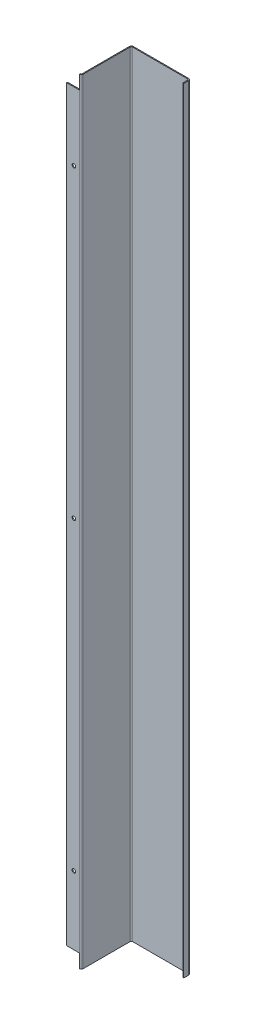
SolidWorks part; units mm, degrees
note: The reader was unsure of these and kept them because the rebuilt part matched: flange length of "Edge-Flange1", "Edge-Flange2", "Edge-Flange3".
material "Galvanized Steel"
ref_plane "Front Plane" through (0, 0, 0) normal (0, 0, 1) x (1, 0, 0)
ref_plane "Top Plane" through (0, 0, 0) normal (0, 1, 0) x (1, 0, 0)
ref_plane "Right Plane" through (0, 0, 0) normal (1, 0, 0) x (0, 0, -1)
sketch "Sketch1" plane through (0, 0, 0) normal (0, 0, 1) x (1, 0, 0)
  line L1 (101.6092, 293.6207) -> (-28.3908, 293.6207)
  line L2 (101.6092, 293.6207) -> (101.6092, -1406.3793)
  line L3 (101.6092, -1406.3793) -> (-28.3908, -1406.3793)
  line L4 (-28.3908, 293.6207) -> (-28.3908, -1406.3793)
  dimension "D1" = 130
  dimension "D2" = 1700
base flange "Base-Flange1" sketch "Sketch1" thickness 2 reverse thickness direction no parameters "D1"=0.5
edge flange "Edge-Flange1" sketch "Sketch8" flange angle 90 flange length 15 flange position material inside bend radius 2.5 thickness 2 relief obround parameters "D6"=10
sketch "Sketch8" plane through (101.6092, 0, 0) normal (1, 0, 0) x (0, 1, 0)
  line L2 (-1406.3793, 0) -> (-1406.3793, 13)
  line L3 (-1406.3793, 13) -> (293.6207, 13)
  line L4 (293.6207, 13) -> (293.6207, 0)
  line L7 (-1406.3793, 0) -> (293.6207, 0) construction
  line L8 (-1406.3793, 0) -> (293.6207, 0)
bend "EdgeBend1" bend radius 2.5 bend angle 90 parameters "D5"=1
edge flange "Edge-Flange2" sketch "Sketch11" flange angle 90 flange length 110 flange position material inside bend radius 2.5 thickness 2 relief obround parameters "D6"=10
sketch "Sketch11" plane through (-28.3908, 0, 0) normal (-1, 0, 0) x (0, -1, 0)
  line L2 (-293.6207, 0) -> (-293.6207, 108)
  line L3 (-293.6207, 108) -> (1406.3793, 108)
  line L4 (1406.3793, 108) -> (1406.3793, 0)
  line L5 (-293.6207, 0) -> (1406.3793, 0) construction
  line L6 (-293.6207, 0) -> (1406.3793, 0)
bend "EdgeBend2" bend radius 2.5 bend angle 90 parameters "D5"=2
edge flange "Edge-Flange3" sketch "Sketch14" flange angle 90 flange length 32 flange position material outside bend radius 2 thickness 2 relief obround parameters "D6"=10
sketch "Sketch14" plane through (-28.3908, 0, 108) normal (0, 0, 1) x (0, 1, 0)
  line L0 (-1406.3793, 0) -> (293.6207, 0) construction
  line L1 (-1406.3793, 0) -> (293.6207, 0)
  line L2 (-1406.3793, 0) -> (-1406.3793, 30)
  line L3 (-1406.3793, 30) -> (293.6207, 30)
  line L4 (293.6207, 30) -> (293.6207, 0)
bend "EdgeBend3" bend radius 2 bend angle 90 parameters "D5"=3
sketch "Sketch15" plane through (0, 0, 110) normal (0, 0, 1) x (1, 0, 0)
  line L0 (-30.3908, -1406.3793) -> (-30.3908, 293.6207) construction
  line L1 (-58.3908, -1406.3793) -> (-30.3908, -1406.3793)
  line L2 (-58.3908, -1406.3793) -> (-58.3908, -1376.3793)
  line L3 (-58.3908, -1376.3793) -> (-30.3908, -1376.3793)
  line L4 (-30.3908, -1406.3793) -> (-30.3908, -1376.3793)
  line L6 (-58.3908, 293.6207) -> (-30.3908, 293.6207)
  line L7 (-58.3908, 293.6207) -> (-58.3908, 263.6207)
  line L8 (-58.3908, 263.6207) -> (-30.3908, 263.6207)
  line L9 (-30.3908, 293.6207) -> (-30.3908, 263.6207)
  dimension "D1" = 30
  dimension "D2" = 30
extrude "Cut-Extrude1" cut sketch "Sketch15" against normal through all both and the other way through all normal cut yes
sketch "Sketch16" plane through (0, 0, 110) normal (0, 0, 1) x (1, 0, 0)
  line L1 (-58.3908, 263.6207) -> (-58.3908, -1376.3793) construction
  line L2 (-23.8908, -1406.3793) -> (97.1092, -1406.3793) construction
  line L3 (97.1092, 293.6207) -> (-23.8908, 293.6207) construction
  circle A0 centre (-42.3908, -1226.3793) radius 4
  circle A1 centre (-42.3908, -556.3793) radius 4
  circle A2 centre (-42.3909, 113.6207) radius 4
  dimension "D1" = 8
  dimension "D2" = 180
  dimension "D6" = 180
  dimension "D4" = 16
  dimension "D5" = 670
  dimension "D3" = 3
extrude "Cut-Extrude2" cut sketch "Sketch16" against normal blind 10 normal cut yes
sketch "Bend-Lines1" [suppressed] plane through (0, 0, 0) normal (0, 1, 0) x (1, 0, 0)
sketch "Bounding-Box1" [suppressed] plane through (0, 0, 0) normal (0, 1, 0) x (1, 0, 0)
sheet metal parameters "Sheet-Metal1" thickness 2 parameters "D1"=0.5
flat pattern "Flat-Pattern1" [suppressed]
sketch "Bend-Lines2" plane through (0, 0, 0) normal (0, 1, 0) x (1, 0, 0)
sketch3d "Bounding-Box2" [suppressed]
  line L0 (-101.6092, 293.6207, 0) -> (-101.6092, -1406.3793, 0) construction
  line L1 (28.3908, 293.6207, 0) -> (28.3908, -1406.3793, 0) construction
  line L2 (-101.6092, 293.6207, 0) -> (28.3908, 293.6207, 0) construction
  line L3 (-101.6092, -1406.3793, 0) -> (28.3908, -1406.3793, 0) construction
sheet metal parameters "Sheet-Metal2" thickness 2 parameters "D1"=0.5
flat pattern "Flat-Pattern1"
sketch "Bend-Lines2" plane through (0, 0, 0) normal (0, 0, 1) x (1, 0, 0)
  line L0 (100.18, -1406.3793) -> (100.18, 293.6207) construction
  line L1 (100.18, -1406.3793) -> (100.18, 293.6207) construction
sketch3d "Bounding-Box2" [suppressed]
  line L0 (113.7508, 293.6207, 0) -> (113.7508, -1406.3793, 0) construction
  line L1 (-28.3908, 293.6207, 0) -> (-28.3908, -1406.3793, 0) construction
  line L2 (113.7508, 293.6207, 0) -> (-28.3908, 293.6207, 0) construction
  line L3 (113.7508, -1406.3793, 0) -> (-28.3908, -1406.3793, 0) construction
bend of the flat pattern "Flatten-<EdgeBend1>1"
sheet metal parameters "Sheet-Metal3" thickness 2 parameters "D1"=0.5
flat pattern "Flat-Pattern1"
sketch "Bend-Lines2" plane through (0, 0, 0) normal (0, 0, 1) x (1, 0, 0)
  line L0 (100.18, -1406.3793) -> (100.18, 293.6207) construction
  line L1 (100.18, -1406.3793) -> (100.18, 293.6207) construction
  line L2 (-26.9616, 293.6207) -> (-26.9616, -1406.3793) construction
  line L3 (-26.9616, 293.6207) -> (-26.9616, -1406.3793) construction
sketch3d "Bounding-Box2" [suppressed]
  line L0 (113.7508, 293.6207, 0) -> (113.7508, -1406.3793, 0) construction
  line L1 (-138.5324, 293.6207, 0) -> (-138.5324, -1406.3793, 0) construction
  line L2 (113.7508, 293.6207, 0) -> (-138.5324, 293.6207, 0) construction
  line L3 (113.7508, -1406.3793, 0) -> (-138.5324, -1406.3793, 0) construction
bend of the flat pattern "Flatten-<EdgeBend1>1"
bend of the flat pattern "Flatten-<EdgeBend2>1"
sheet metal parameters "Sheet-Metal4" thickness 2 parameters "D1"=0.5
flat pattern "Flat-Pattern1"
sketch "Bend-Lines2" plane through (0, 0, 0) normal (0, 0, 1) x (1, 0, 0)
  line L0 (100.18, -1406.3793) -> (100.18, 293.6207) construction
  line L1 (100.18, -1406.3793) -> (100.18, 293.6207) construction
  line L2 (-26.9616, 293.6207) -> (-26.9616, -1406.3793) construction
  line L3 (-26.9616, 293.6207) -> (-26.9616, -1406.3793) construction
  line L4 (-137.3178, -1406.3793) -> (-137.3178, 293.6207) construction
  line L5 (-137.3178, -1406.3793) -> (-137.3178, 293.6207) construction
sketch3d "Bounding-Box2" [suppressed]
  line L0 (113.7508, 293.6207, 0) -> (113.7508, -1406.3793, 0) construction
  line L1 (-171.1032, 293.6207, 0) -> (-171.1032, -1406.3793, 0) construction
  line L2 (113.7508, 293.6207, 0) -> (-171.1032, 293.6207, 0) construction
  line L3 (113.7508, -1406.3793, 0) -> (-171.1032, -1406.3793, 0) construction
bend of the flat pattern "Flatten-<EdgeBend1>1"
bend of the flat pattern "Flatten-<EdgeBend2>1"
bend of the flat pattern "Flatten-<EdgeBend3>1"
sheet metal parameters "Sheet-Metal5" thickness 2 parameters "D1"=0.5
flat pattern "Flat-Pattern1"
sketch "Bend-Lines2" plane through (0, 0, 0) normal (0, 0, 1) x (1, 0, 0)
  line L0 (100.18, -1406.3793) -> (100.18, 293.6207) construction
  line L1 (100.18, -1406.3793) -> (100.18, 293.6207) construction
  line L2 (-26.9616, 293.6207) -> (-26.9616, -1406.3793) construction
  line L3 (-26.9616, 293.6207) -> (-26.9616, -1406.3793) construction
  line L4 (-137.3178, -1406.3793) -> (-137.3178, 293.6207) construction
  line L5 (-137.3178, -1406.3793) -> (-137.3178, 293.6207) construction
sketch3d "Bounding-Box2" [suppressed]
  line L0 (113.7508, 293.6207, 0) -> (113.7508, -1406.3793, 0) construction
  line L1 (-171.1032, 293.6207, 0) -> (-171.1032, -1406.3793, 0) construction
  line L2 (113.7508, 293.6207, 0) -> (-171.1032, 293.6207, 0) construction
  line L3 (113.7508, -1406.3793, 0) -> (-171.1032, -1406.3793, 0) construction
bend of the flat pattern "Flatten-<EdgeBend1>1"
bend of the flat pattern "Flatten-<EdgeBend2>1"
bend of the flat pattern "Flatten-<EdgeBend3>1"
sheet metal parameters "Sheet-Metal6" thickness 2 parameters "D1"=0.5
flat pattern "Flat-Pattern1"
sketch "Bend-Lines2" plane through (0, 0, 110) normal (0, 0, 1) x (1, 0, 0)
  line L0 (207.0683, -1406.3793) -> (207.0683, 293.6207) construction
  line L1 (207.0683, -1406.3793) -> (207.0683, 293.6207) construction
  line L2 (80.5705, -1406.3793) -> (80.5705, 293.6207) construction
  line L3 (80.5705, -1406.3793) -> (80.5705, 293.6207) construction
  line L4 (-28.0346, -1406.3793) -> (-28.0346, 293.6207) construction
  line L5 (-28.0346, -1406.3793) -> (-28.0346, 293.6207) construction
sketch3d "Bounding-Box2" [suppressed]
  line L0 (220.3172, 293.6207, 0) -> (220.3172, -1406.3793, 0) construction
  line L1 (-58.3908, 293.6207, 0) -> (-58.3908, -1406.3793, 0) construction
  line L2 (220.3172, 293.6207, 0) -> (-58.3908, 293.6207, 0) construction
  line L3 (220.3172, -1406.3793, 0) -> (-58.3908, -1406.3793, 0) construction
bend of the flat pattern "Flatten-<EdgeBend1>1"
bend of the flat pattern "Flatten-<EdgeBend2>1"
bend of the flat pattern "Flatten-<EdgeBend3>1"
